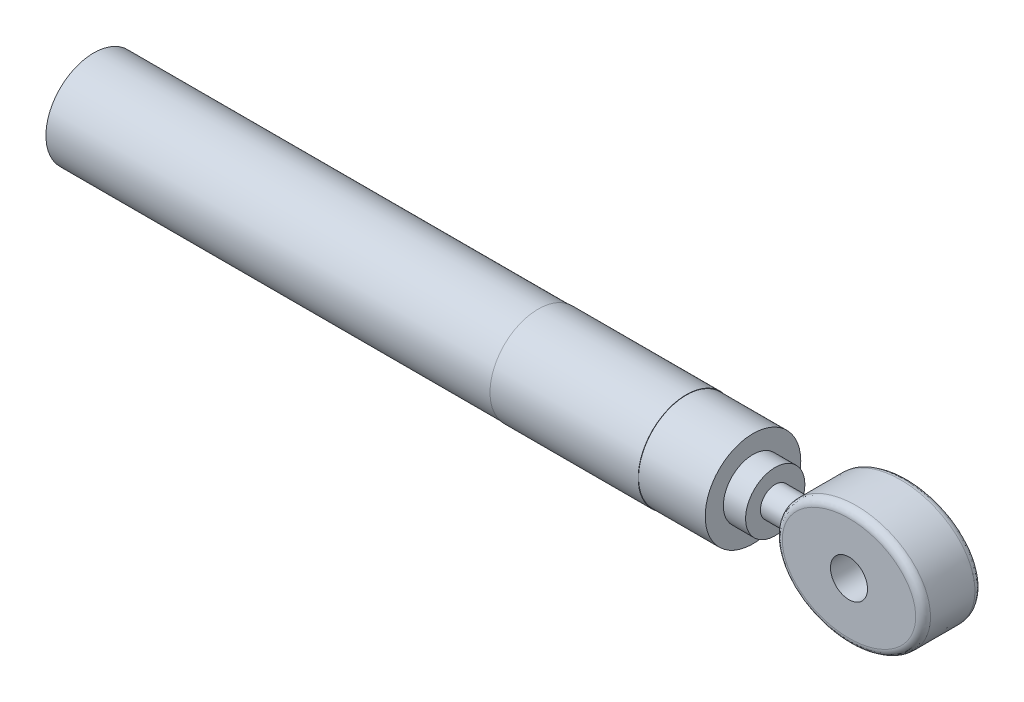
SolidWorks part; units mm, degrees
ref_plane "Front Plane" through (0, 0, 0) normal (0, 0, 1) x (1, 0, 0)
ref_plane "Top Plane" through (0, 0, 0) normal (0, 1, 0) x (1, 0, 0)
ref_plane "Right Plane" through (0, 0, 0) normal (1, 0, 0) x (0, 0, -1)
sketch "Sketch1" plane through (0, 0, 0) normal (1, 0, 0) x (0, 0, -1)
  circle A0 centre (0, 0) radius 6.5
  dimension "D1" = 13
extrude "Boss-Extrude1" add sketch "Sketch1" along normal blind 20
sketch "Sketch2" plane through (20, 0, 0) normal (1, 0, 0) x (0, 0, -1)
  circle A0 centre (0, 0) radius 6.45
  dimension "D1" = 12.9
extrude "Boss-Extrude2" add sketch "Sketch2" along normal blind 9
sketch "Sketch3" plane through (29, 0, 0) normal (1, 0, 0) x (0, 0, -1)
  circle A0 centre (0, 0) radius 4
  dimension "D1" = 8
extrude "Boss-Extrude3" add sketch "Sketch3" along normal blind 3
sketch "Sketch4" plane through (0, 0, 0) normal (0, 0, 1) x (1, 0, 0)
  ellipse E0 centre (45.9597, 0) end of major axis (35.9597, 0) minor radius 8
  dimension "D1" = 16
  dimension "D2" = 20
extrude "Boss-Extrude4" add sketch "Sketch4" along normal blind 4 and the other way blind 4 separate body
fillet "Fillet2" radius 1 2 edges at (35.9597, 0, -4) (35.9597, 0, 4)
sketch "Sketch5" plane through (32, 0, 0) normal (1, 0, 0) x (0, 0, -1)
  circle A0 centre (0, 0) radius 2
  dimension "D1" = 4
extrude "Boss-Extrude5" add sketch "Sketch5" along normal blind 11.5 contours A0
sketch "Sketch8" plane through (0, 0, 4) normal (0, 0, 1) x (1, 0, 0)
  circle A0 centre (45.9597, 0) radius 2.5
  dimension "D1" = 5
extrude "Cut-Extrude1" cut sketch "Sketch8" against normal through all
sketch "Sketch9" plane through (0, 0, 0) normal (-1, 0, 0) x (0, 0, 1)
  circle A0 centre (0, 0) radius 6.45
  dimension "D1" = 12.9
extrude "Boss-Extrude6" add sketch "Sketch9" along normal blind 60
sketch "Sketch10" plane through (-60, 0, 0) normal (-1, 0, 0) x (0, 0, 1)
  circle A0 centre (0, 0) radius 2
  dimension "D1" = 4
extrude "Cut-Extrude2" cut sketch "Sketch10" against normal blind 10
sketch "Sketch11" plane through (-60, 0, 0) normal (-1, 0, 0) x (0, 0, 1)
  circle A0 centre (0, 0) radius 2
  circle A1 centre (0, 0) radius 3.6749
extrude "Boss-Extrude7" add sketch "Sketch11" along normal blind 1
